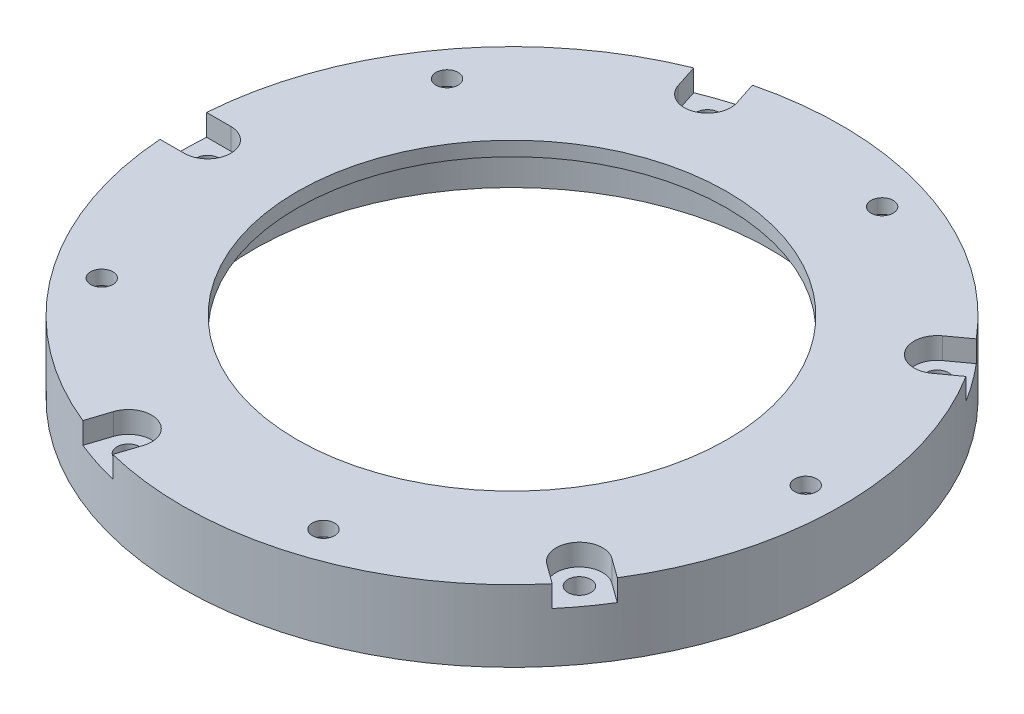
SolidWorks part; units mm, degrees
ref_plane "Front Plane" through (0, 0, 0) normal (0, 0, 1) x (1, 0, 0)
ref_plane "Top Plane" through (0, 0, 0) normal (0, 1, 0) x (1, 0, 0)
ref_plane "Right Plane" through (0, 0, 0) normal (1, 0, 0) x (0, 0, -1)
sketch "Sketch1" plane through (0, 0, 0) normal (0, 1, 0) x (1, 0, 0)
  circle A0 centre (0, 0) radius 46
  circle A1 centre (0, 0) radius 36.05
  circle A2 centre (0, 0) radius 30
  dimension "D1" = 60
  dimension "D2" = 72.1
  dimension "D3" = 92
extrude "Boss-Extrude1" add sketch "Sketch1" against normal blind 2 contours A1 A2 | A0 A1 region at (-44.6989, 0, 0) region at (-35.0304, 0, 0)
extrude "Boss-Extrude2" add sketch "Sketch1<3>" against normal blind 8 from surface contours A0 A1 region at (-44.6989, 0, 0) starting at face at (0, -2, 30)
sketch "Sketch1<3>" plane through (0, 0, 0) normal (0, 1, 0) x (1, 0, 0) same geometry as "Sketch1"
hole_wizard "CBORE for M3 SHCS2" positions "Sketch6" profile "Sketch7" counterbore size "M3" standard "ANSI Metric" end condition through all
sketch "Sketch6" plane through (0, 0, 0) normal (0, 1, 0) x (1, 0, 0)
  line L0 (0, 0) -> (-42.5, 0) construction
  point P2 (-42.5, 0)
  dimension "D1" = 42.5
sketch "Sketch7" plane through (-42.5, 0, 0) normal (1, 0, 0) x (0, 0, 1)
  line L0 (0, 0) -> (0, 10)
  line L1 (0, 10) -> (1.6, 10)
  line L3 (1.6, 10) -> (1.6, 3)
  line L4 (1.6, 3) -> (3.25, 3)
  line L5 (3.25, 3) -> (3.25, 0)
  line L7 (3.25, 0) -> (0, 0)
  line L11 (0, -6.35) -> (0, 107.95) construction
  dimension "Thru Hole Dia." = 3.2
  dimension "Thru Hole Depth" = 10
  dimension "C'Bore Dia." = 6.5
  dimension "C'Bore Depth" = 3
sketch "Sketch8" plane through (0, -3, 0) normal (0, 1, 0) x (1, 0, 0)
  line L1 (-42.5, 3.25) -> (-52.5, 3.25)
  line L2 (-42.5, 3.25) -> (-42.5, -3.25)
  line L3 (-42.5, -3.25) -> (-52.5, -3.25)
  line L4 (-52.5, 3.25) -> (-52.5, -3.25)
  circle A3 centre (-42.5, 0) radius 3.25
  circle A5 centre (-42.5, 0) radius 3.25
  circle M5 centre (-42.5, 0) radius 3.25
  circle M6 centre (-42.5, 0) radius 1.6
  dimension "D2" = 10
  dimension "D1" = 0
extrude "Cut-Extrude1" cut sketch "Sketch8" along normal through all contours L2 M5 M6 | L1 L4 M5 | L4 L3 M5 region at (-48.7409, -3, 0) region at (-44.1034, -3, 0)
pattern_circular "CirPattern1" count 5 over 360 about axis through (0, -2, 0) along (0, 1, 0) of "Cut-Extrude1", "CBORE for M3 SHCS2" reverse direction yes
sketch "Sketch9" plane through (0, 0, 0) normal (0, 1, 0) x (1, 0, 0)
  line L0 (0, 0) -> (41, 0) construction
  line L2 (41, 3.1754) -> (38.25, 1.5877)
  line L3 (38.25, 1.5877) -> (38.25, -1.5877)
  line L4 (38.25, -1.5877) -> (41, -3.1754)
  line L5 (41, -3.1754) -> (43.75, -1.5877)
  line L6 (43.75, -1.5877) -> (43.75, 1.5877)
  line L7 (43.75, 1.5877) -> (41, 3.1754)
  circle A0 centre (41, 0) radius 1.55
  circle A1 centre (41, 0) radius 2.75 construction
  dimension "D2" = 3.1
  dimension "D1" = 41
  dimension "D3" = 5.5
extrude "Cut-Extrude2" cut sketch "Sketch9" against normal through all contours A0 region at (41, 0, 0)
extrude "Cut-Extrude3" cut sketch "Sketch9<3>" against normal through all from offset 2 contours L6 L7 L2 L3 L4 L5 A0 region at (42.333, 0, -2.3088) offset against normal yes
sketch "Sketch9<3>" plane through (0, 0, 0) normal (0, 1, 0) x (1, 0, 0) same geometry as "Sketch9"
pattern_circular "CirPattern2" count 5 over 360 about axis through (0, -10, 0) along (0, 1, 0) of "Cut-Extrude2", "Cut-Extrude3" reverse direction yes
equation "\"Ratio\"= 15"
equation "\"Hull Diameter\"= 92"
equation "\"Fixed Ring Diameter\"= 76"
equation "\"Fixed Pin Diameter\"= 6"
equation "\"Output Ring Diameter\"= 40"
equation "\"Output Pin Diameter\"= 6"
equation "\"Disk Bearing Inner Diameter\"= 9"
equation "\"Disk Bearing Outer Diameter\"= 17"
equation "\"Disk Bearing Height\"= 5"
equation "\"Shaft Bearing Inner Diameter\"= 15"
equation "\"Shaft Bearing Outer Diameter\"= 21"
equation "\"Shaft Bearing Height\"= 4"
equation "\"Eccentricity\"= 1.5"
equation "\"Disk Height\"= 8"
equation "\"Disk Spacing\"= 5"
equation "\"Hull Height\"= 40"
equation "\"Shaft End Bearing Inner Diameter\"= 12"
equation "\"Shaft End Bearing Outer Diameter\"= 18"
equation "\"Shaft End Bearing Height\"= 4"
equation "\"Output Bearing Inner Diameter\"= 55"
equation "\"Output Bearing Outer Diameter\"= 72"
equation "\"Outer Bearing Height\"= 9"
equation "\"D1@Sketch1\"=\"Output Bearing Inner Diameter\"+5"
equation "\"D2@Sketch1\"=\"Output Bearing Outer Diameter\"+0.1"
equation "\"D3@Sketch1\"=\"Hull Diameter\""
